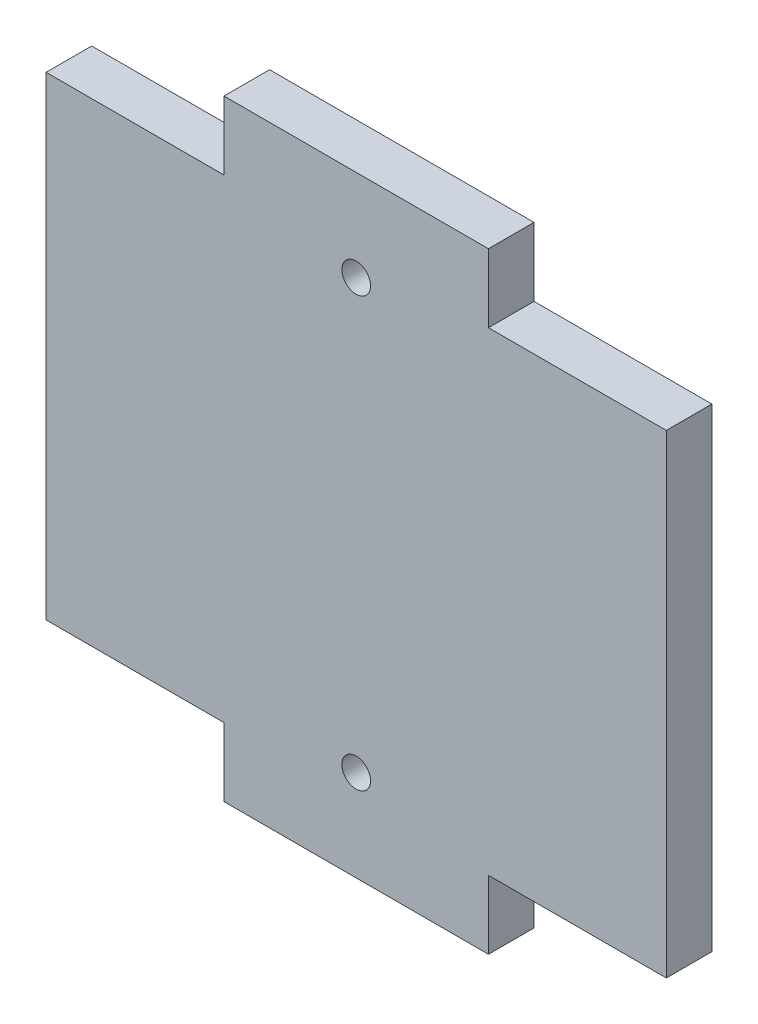
SolidWorks part; units mm, degrees
ref_plane "Front Plane" through (0, 0, 0) normal (0, 0, 1) x (1, 0, 0)
ref_plane "Top Plane" through (0, 0, 0) normal (0, 1, 0) x (1, 0, 0)
ref_plane "Right Plane" through (0, 0, 0) normal (1, 0, 0) x (0, 0, -1)
sketch "Sketch1" plane through (0, 0, 0) normal (0, 0, 1) x (1, 0, 0)
  line L0 (0, 0) -> (0, 10.6363) construction
  line L1 (7.62, -5.08) -> (-7.62, -5.08)
  line L2 (7.62, -5.08) -> (7.62, 5.08)
  line L3 (7.62, 5.08) -> (-7.62, 5.08)
  line L4 (-7.62, -5.08) -> (-7.62, 5.08)
  line L5 (7.62, -5.08) -> (-7.62, 5.08) construction
  line L6 (7.62, 5.08) -> (-7.62, -5.08) construction
  line L7 (10.795, -8.255) -> (-10.795, -8.255)
  line L8 (10.795, -8.255) -> (10.795, 8.255)
  line L9 (10.795, 8.255) -> (-10.795, 8.255)
  line L10 (-10.795, -8.255) -> (-10.795, 8.255)
  line L11 (10.795, -8.255) -> (-10.795, 8.255) construction
  line L12 (10.795, 8.255) -> (-10.795, -8.255) construction
  line L13 (0, 0) -> (10.795, 0) construction
  line L14 (-4.6037, 8.255) -> (4.6037, 8.255)
  line L15 (-4.6037, 8.255) -> (-4.6037, 10.6363)
  line L16 (-4.6037, 10.6363) -> (4.6037, 10.6363)
  line L17 (4.6037, 8.255) -> (4.6037, 10.6363)
  line L18 (4.6037, -8.255) -> (4.6037, -10.6363)
  line L19 (-4.6037, -10.6363) -> (4.6037, -10.6363)
  line L20 (-4.6037, -8.255) -> (-4.6037, -10.6363)
  line L21 (-4.6037, -8.255) -> (4.6037, -8.255)
  circle A0 centre (0, 7.4613) radius 0.5
  circle A1 centre (0, -7.4613) radius 0.5
  point P0 (0, 0)
  point P6 (0, 0)
  point P17 (0, 10.6363)
  dimension "D5" = 1
  dimension "D1" = 15.24
  dimension "D2" = 10.16
  dimension "D3" = 3.175
  dimension "D4" = 3.175
  dimension "D6" = 2.3813
  dimension "D7" = 3.175
  dimension "D8" = 9.2075
extrude "Boss-Extrude1" add sketch "Sketch1" along normal blind 1.5875 contours L10 L7 L8 L9 L1 L4 L3 L2 A0 A1 | L4 L1 L2 L3 | L9 L17 L16 L15 | L7 L20 L19 L18 region at (0, 0, 0) region at (7.6994, -7.9832, 0) region at (0, -9.4456, 0) region at (0, 9.4456, 0)
extrude "Boss-Extrude2" add sketch "Sketch1<3>" against normal blind 3.175 contours L3 L4 L1 L2
sketch "Sketch1<3>" plane through (0, 0, 0) normal (0, 0, 1) x (1, 0, 0) same geometry as "Sketch1"
